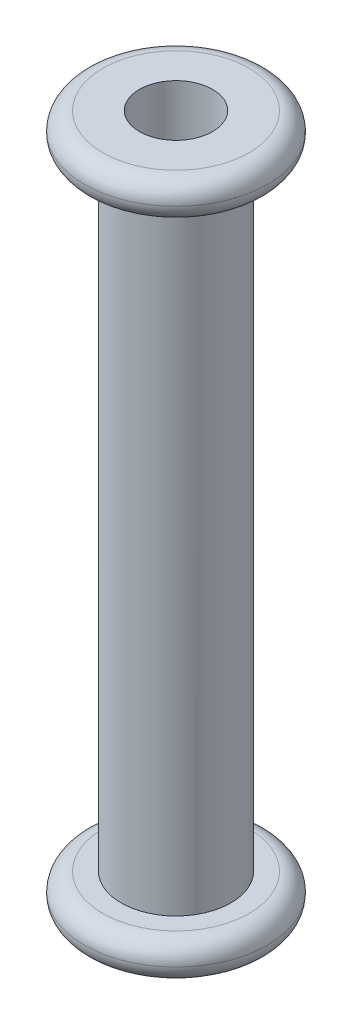
SolidWorks part; units mm, degrees
ref_plane "Front Plane" through (0, 0, 0) normal (0, 0, 1) x (1, 0, 0)
ref_plane "Top Plane" through (0, 0, 0) normal (0, 1, 0) x (1, 0, 0)
ref_plane "Right Plane" through (0, 0, 0) normal (1, 0, 0) x (0, 0, -1)
sketch "Sketch1" plane through (0, 0, 0) normal (0, 1, 0) x (1, 0, 0)
  circle A0 centre (0, 0) radius 2
  circle A1 centre (0, 0) radius 3
  dimension "D1" = 4
  dimension "D2" = 1
extrude "Boss-Extrude1" add sketch "Sketch1" along normal blind 38
sketch "Sketch2" plane through (0, 0, 0) normal (0, -1, 0) x (1, 0, 0)
  circle A0 centre (0, 0) radius 3 construction
  circle A1 centre (0, 0) radius 3
  circle A2 centre (0, 0) radius 5
  dimension "D1" = 2
extrude "Boss-Extrude2" add sketch "Sketch2" against normal blind 2
sketch "Sketch3" plane through (0, 38, 0) normal (0, 1, 0) x (1, 0, 0)
  circle A1 centre (0, 0) radius 3 construction
  circle A2 centre (0, 0) radius 5
  circle A3 centre (0, 0) radius 5
  circle A4 centre (0, 0) radius 3
  dimension "D1" = 2
extrude "Boss-Extrude3" add sketch "Sketch3" against normal blind 2
fillet "Fillet4" radius 1 1 edges at (0, 0, -5)
fillet "Fillet5" radius 1 1 edges at (0, 2, -5)
fillet "Fillet6" radius 1 2 edges at (0, 36, 5) (0, 38, 5)
